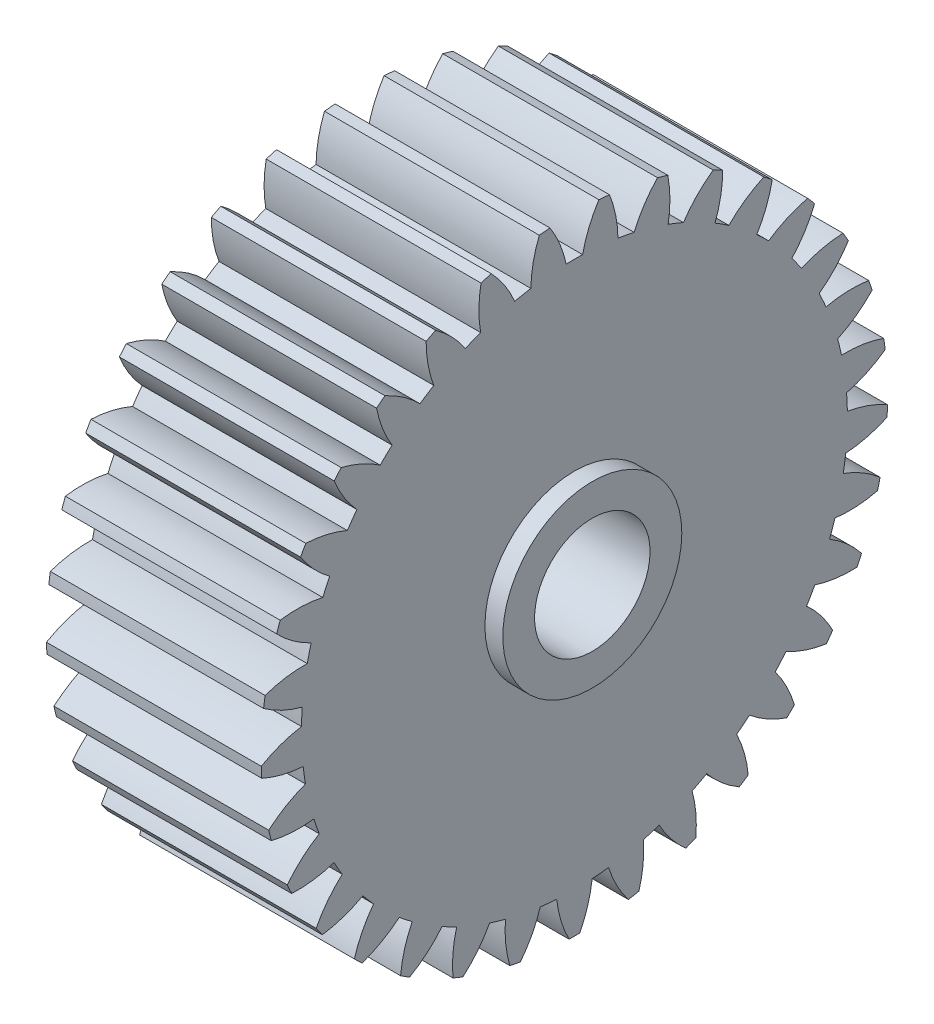
SolidWorks part; units mm, degrees
ref_plane "Plane1" through (0, 0, 0) normal (0, 0, 1) x (1, 0, 0)
ref_plane "Plane2" through (0, 0, 0) normal (0, 1, 0) x (1, 0, 0)
ref_plane "Plane3" through (0, 0, 0) normal (1, 0, 0) x (0, 0, -1)
sketch "HoldingSke" plane through (0, 0, 0) normal (0, 1, 0) x (1, 0, 0)
  line L0 (0, 0) -> (0.8387, -0.5446)
  line L1 (-15, 0) -> (100, 0) construction
  line L2 (0, 0) -> (-2.1039, 2.3779)
  line L3 (0, 0) -> (-11.863, 4.5341)
  line L4 (0, 0) -> (7.2428, 4.7035)
  line L5 (0, 0) -> (-46.8476, -17.4728)
  line L6 (0, 0) -> (-6.6317, -4.4744)
  line L7 (-2.1039, 2.3779) -> (8.6586, 51.2059)
  line L8 (-76.2, 54.61) -> (-74.4, 54.61)
  line L9 (-71.009, 38.7566) -> (-53.1078, 45.2721)
  line L10 (-76.2, 71.12) -> (104.1128, 71.12)
  line L11 (0, 0) -> (-8, 0)
  line L12 (-76.2, 101.6) -> (-76.162, 101.6)
  line L13 (24.9733, 27.94) -> (52.9518, 28.4284)
  line L14 (24.9733, 27.94) -> (24.9743, 27.94)
  line L15 (24.9733, 27.94) -> (100.4006, 29.5858)
  line L16 (-63.627, -1) -> (-12.827, -1)
  circle A0 centre (0, 0) radius 5
  circle A1 centre (0, 0) radius 15.249
  circle A2 centre (0, 0) radius 37.5
  circle A3 centre (0, 0) radius 5
  dimension "MHD" = 30.498
  dimension "Hub_dia" = 75
  dimension "Bore" = 10
  dimension "MBD" = 10
  dimension "Num_teeth" = 33
  dimension "Pitch" = 1
  dimension "Overall_len" = 50
  dimension "Show_teeth" = 33
  dimension "Thickness" = 8
  dimension "OAL" = 50.0001
  dimension "T_dim" = 1.8
  dimension "Ap" = 20
  dimension "H" = 19.05
  dimension "Pitch_radius" = 180.3128
  dimension "Width" = 8
  dimension "Backlash" = 0.038
  dimension "Addendum_fac" = 1
  dimension "Dedendum_fac" = 1.25
  dimension "Clearance_fac" = 0.25
  dimension "Dedendum_add" = 0.001
  dimension "Module" = 1
sketch "BasProSke" plane through (0, 0, 0) normal (0, 1, 0) x (1, 0, 0)
  line L0 (-10, 0) -> (60, 0) construction
  line L1 (0, 0) -> (0, 17.5)
  line L2 (0, 0) -> (6, 0)
  line L3 (6, 0) -> (6, 17.5)
  line L4 (6, 17.5) -> (0, 17.5)
  dimension "Thickness" = 6
  dimension "Diameter" = 35
revolve "Base-Revolve" add sketch "BasProSke" angle 360 about L0
sketch "TooCutSke" plane through (0, 0, 0) normal (1, 0, 0) x (0, 0, -1)
  line L1 (0, 0) -> (0, 107) construction
  line L2 (0, 0) -> (-0.8516, 16.478) construction
  line L3 (0, 0) -> (-3.1339, 32.8194) construction
  line L4 (-0.8516, 16.478) -> (-1.5669, 16.4097) construction
  arc A0 (0.46, 15.2421) -> (-0.46, 15.2421) centre (0, 0) ccw
  arc A1 (1.3819, 17.4708) -> (-1.3819, 17.4708) centre (0, 0) ccw
  circle A2 centre (0, 0) radius 16.5 construction
  circle A3 centre (0, 0) radius 15.5049 construction
  arc A4 (-0.46, 15.2421) -> (-1.3819, 17.4708) centre (-6.9172, 13.8764) ccw
  arc A5 (1.3819, 17.4708) -> (0.46, 15.2421) centre (6.9172, 13.8764) ccw
  dimension "Root_dia" = 30.498
  dimension "Overcut_dia" = 35.0508
  dimension "Pitch_dia" = 33
  dimension "Base_dia" = 31.0099
  dimension "Flank_rad" = 6.6
  dimension "Half_ang" = 5.455
  dimension "Half_CT" = 0.7186
extrude "ToothCut" cut sketch "TooCutSke" along normal through all
fillet "Breaks" [suppressed] radius 0.02 tangent propagation no
fillet "RootFillets" [suppressed] radius 0.251
pattern_circular "TeethCuts" count 33 every 10.909 about axis through (-10, 0, 0) along (1, 0, 0) of "ToothCut", "RootFillets", "Breaks"
sketch "HubNeaOneSke" plane through (0, 0, 0) normal (-1, 0, 0) x (0, 0, 1)
  circle A0 centre (0, 0) radius 15.249
  dimension "Diameter" = 30.498
extrude "HubNearOne" [suppressed] add sketch "HubNeaOneSke" along normal blind 44.0001
sketch "HubNeaBotSke" plane through (0, 0, 0) normal (-1, 0, 0) x (0, 0, 1)
  circle A0 centre (0, 0) radius 15.249
  dimension "Diameter" = 30.498
extrude "HubNearBoth" [suppressed] add sketch "HubNeaBotSke" along normal blind 22
ref_plane "FarPln" through (6, 0, 0) normal (1, 0, 0) x (0, 0, -1)
sketch "HubFarSke" plane through (6, 0, 0) normal (1, 0, 0) x (0, 0, -1)
  circle A0 centre (0, 0) radius 15.249
  dimension "Diameter" = 30.498
extrude "HubFar" [suppressed] add sketch "HubFarSke" along normal blind 22
sketch "BorSke" plane through (0, 0, 0) normal (1, 0, 0) x (0, 0, -1)
  circle A0 centre (0, 0) radius 5
  dimension "Diameter" = 10
extrude "Bore" cut sketch "BorSke" along normal mid plane 100.0001
sketch "KeySke" plane through (0, 0, 0) normal (1, 0, 0) x (0, 0, -1)
  line L0 (-2, 0) -> (-2, 6.8)
  line L1 (-2, 6.8) -> (2, 6.8)
  line L2 (2, 6.8) -> (2, 0)
  line L3 (0, 0) -> (0, 34) construction
  line L4 (-2, 0) -> (2, 0)
  dimension "Offset" = 6.8
  dimension "Width" = 4
extrude "Keyway" [suppressed] cut sketch "KeySke" along normal mid plane 100.0001
pattern_circular "Keyway2" [suppressed] count 2 every 90 about axis through (-10, 0, 0) along (1, 0, 0) reverse direction yes
sketch "Croquis1" plane through (6, 0, 0) normal (1, 0, 0) x (0, 0, -1)
  circle A0 centre (0, 0) radius 5 construction
  circle A1 centre (0, 0) radius 5
  circle A2 centre (0, 0) radius 3.225
  dimension "D1" = 6.45
extrude "Saliente-Extruir2" add sketch "Croquis1" along normal blind 1 and the other way through all
sketch "Croquis2" plane through (0, 0, 0) normal (-1, 0, 0) x (0, 0, 1)
  circle A0 centre (0, 0) radius 3.225 construction
  circle A1 centre (0, 0) radius 3.225
  arc A132 (15.2029, 1.1848) -> (17.3618, 2.1948) centre (13.5316, 7.5696) ccw
  arc A133 (17.3618, 2.1948) -> (17.2769, 2.7855) centre (0, 0) ccw
  arc A134 (17.2769, 2.7855) -> (14.9209, 3.1464) centre (15.1161, -3.4507) ccw
  arc A135 (14.9209, 3.1464) -> (14.704, 4.0405) centre (0, 0) ccw
  arc A136 (14.704, 4.0405) -> (16.6327, 5.4409) centre (11.8545, 9.9937) ccw
  arc A137 (16.6327, 5.4409) -> (16.4375, 6.0049) centre (0, 0) ccw
  arc A138 (16.4375, 6.0049) -> (14.0558, 5.9133) centre (15.4959, -0.5276) ccw
  arc A139 (14.0558, 5.9133) -> (13.6736, 6.7502) centre (0, 0) ccw
  arc A140 (13.6736, 6.7502) -> (15.3024, 8.4903) centre (9.7489, 12.0566) ccw
  arc A141 (15.3024, 8.4903) -> (15.004, 9.0072) centre (0, 0) ccw
  arc A142 (15.004, 9.0072) -> (12.6827, 8.4665) centre (15.3158, 2.4145) ccw
  arc A143 (12.6827, 8.4665) -> (12.149, 9.216) centre (0, 0) ccw
  arc A144 (12.149, 9.216) -> (13.4191, 11.2329) centre (7.291, 13.6837) ccw
  arc A145 (13.4191, 11.2329) -> (13.0283, 11.6839) centre (0, 0) ccw
  arc A146 (13.0283, 11.6839) -> (10.8512, 10.7137) centre (14.582, 5.2694) ccw
  arc A147 (10.8512, 10.7137) -> (10.1853, 11.3487) centre (0, 0) ccw
  arc A148 (10.1853, 11.3487) -> (11.0508, 13.5695) centre (4.5696, 14.8163) ccw
  arc A149 (11.0508, 13.5695) -> (10.5816, 13.9384) centre (0, 0) ccw
  arc A150 (10.5816, 13.9384) -> (8.6275, 12.5737) centre (13.3213, 7.9339) ccw
  arc A151 (8.6275, 12.5737) -> (7.8535, 13.0712) centre (0, 0) ccw
  arc A152 (7.8535, 13.0712) -> (8.283, 15.4156) centre (1.683, 15.4133) ccw
  arc A153 (8.283, 15.4156) -> (7.7526, 15.6891) centre (0, 0) ccw
  arc A154 (7.7526, 15.6891) -> (6.092, 13.9793) centre (11.5791, 10.3116) ccw
  arc A155 (6.092, 13.9793) -> (5.2378, 14.3212) centre (0, 0) ccw
  arc A156 (5.2378, 14.3212) -> (5.2159, 16.7046) centre (-1.2644, 15.4533) ccw
  arc A157 (5.2159, 16.7046) -> (4.6433, 16.8728) centre (0, 0) ccw
  arc A158 (4.6433, 16.8728) -> (3.3363, 14.8796) centre (9.4183, 12.3166) ccw
  arc A159 (3.3363, 14.8796) -> (2.4329, 15.0537) centre (0, 0) ccw
  arc A160 (2.4329, 15.0537) -> (1.9603, 17.3899) centre (-4.1661, 14.9347) ccw
  arc A161 (1.9603, 17.3899) -> (1.3662, 17.4466) centre (0, 0) ccw
  arc A162 (1.3662, 17.4466) -> (0.46, 15.2421) centre (6.9172, 13.8764) ccw
  arc A163 (0.46, 15.2421) -> (-0.46, 15.2421) centre (0, 0) ccw
  arc A164 (-0.46, 15.2421) -> (-1.3662, 17.4466) centre (-6.9172, 13.8764) ccw
  arc A165 (-1.3662, 17.4466) -> (-1.9603, 17.3899) centre (0, 0) ccw
  arc A166 (-1.9603, 17.3899) -> (-2.4329, 15.0537) centre (4.1661, 14.9347) ccw
  arc A167 (-2.4329, 15.0537) -> (-3.3363, 14.8796) centre (0, 0) ccw
  arc A168 (-3.3363, 14.8796) -> (-4.6433, 16.8728) centre (-9.4183, 12.3166) ccw
  arc A169 (-4.6433, 16.8728) -> (-5.2159, 16.7046) centre (0, 0) ccw
  arc A170 (-5.2159, 16.7046) -> (-5.2378, 14.3212) centre (1.2644, 15.4533) ccw
  arc A171 (-5.2378, 14.3212) -> (-6.092, 13.9793) centre (0, 0) ccw
  arc A172 (-6.092, 13.9793) -> (-7.7526, 15.6891) centre (-11.5791, 10.3116) ccw
  arc A173 (-7.7526, 15.6891) -> (-8.283, 15.4156) centre (0, 0) ccw
  arc A174 (-8.283, 15.4156) -> (-7.8535, 13.0712) centre (-1.683, 15.4133) ccw
  arc A175 (-7.8535, 13.0712) -> (-8.6275, 12.5737) centre (0, 0) ccw
  arc A176 (-8.6275, 12.5737) -> (-10.5816, 13.9384) centre (-13.3213, 7.9339) ccw
  arc A177 (-10.5816, 13.9384) -> (-11.0508, 13.5695) centre (0, 0) ccw
  arc A178 (-11.0508, 13.5695) -> (-10.1853, 11.3487) centre (-4.5696, 14.8163) ccw
  arc A179 (-10.1853, 11.3487) -> (-10.8512, 10.7137) centre (0, 0) ccw
  arc A180 (-10.8512, 10.7137) -> (-13.0283, 11.6839) centre (-14.582, 5.2694) ccw
  arc A181 (-13.0283, 11.6839) -> (-13.4191, 11.2329) centre (0, 0) ccw
  arc A182 (-13.4191, 11.2329) -> (-12.149, 9.216) centre (-7.291, 13.6837) ccw
  arc A183 (-12.149, 9.216) -> (-12.6827, 8.4665) centre (0, 0) ccw
  arc A184 (-12.6827, 8.4665) -> (-15.004, 9.0072) centre (-15.3158, 2.4145) ccw
  arc A185 (-15.004, 9.0072) -> (-15.3024, 8.4903) centre (0, 0) ccw
  arc A186 (-15.3024, 8.4903) -> (-13.6736, 6.7502) centre (-9.7489, 12.0566) ccw
  arc A187 (-13.6736, 6.7502) -> (-14.0558, 5.9133) centre (0, 0) ccw
  arc A188 (-14.0558, 5.9133) -> (-16.4375, 6.0049) centre (-15.4959, -0.5276) ccw
  arc A189 (-16.4375, 6.0049) -> (-16.6327, 5.4409) centre (0, 0) ccw
  arc A190 (-16.6327, 5.4409) -> (-14.704, 4.0405) centre (-11.8545, 9.9937) ccw
  arc A191 (-14.704, 4.0405) -> (-14.9209, 3.1464) centre (0, 0) ccw
  arc A192 (-14.9209, 3.1464) -> (-17.2769, 2.7855) centre (-15.1161, -3.4507) ccw
  arc A193 (-17.2769, 2.7855) -> (-17.3618, 2.1948) centre (0, 0) ccw
  arc A194 (-17.3618, 2.1948) -> (-15.2029, 1.1848) centre (-13.5316, 7.5696) ccw
  arc A195 (-15.2029, 1.1848) -> (-15.2467, 0.2657) centre (0, 0) ccw
  arc A196 (-15.2467, 0.2657) -> (-17.4918, -0.5345) centre (-14.1898, -6.2491) ccw
  arc A197 (-17.4918, -0.5345) -> (-17.4634, -1.1306) centre (0, 0) ccw
  arc A198 (-17.4634, -1.1306) -> (-15.1524, -1.7138) centre (-14.7196, 4.872) ccw
  arc A199 (-15.1524, -1.7138) -> (-15.0214, -2.6245) centre (0, 0) ccw
  arc A200 (-15.0214, -2.6245) -> (-17.0746, -3.8352) centre (-12.7508, -8.8216) ccw
  arc A201 (-17.0746, -3.8352) -> (-16.9339, -4.4152) centre (0, 0) ccw
  arc A202 (-16.9339, -4.4152) -> (-14.5542, -4.5505) centre (-15.3756, 1.9982) ccw
  arc A203 (-14.5542, -4.5505) -> (-14.2533, -5.4199) centre (0, 0) ccw
  arc A204 (-14.2533, -5.4199) -> (-16.0402, -6.9973) centre (-10.8508, -11.0753) ccw
  arc A205 (-16.0402, -6.9973) -> (-15.7923, -7.5401) centre (0, 0) ccw
  arc A206 (-15.7923, -7.5401) -> (-13.43, -7.2226) centre (-15.4759, -0.9477) ccw
  arc A207 (-13.43, -7.2226) -> (-12.97, -8.0194) centre (0, 0) ccw
  arc A208 (-12.97, -8.0194) -> (-14.4261, -9.9064) centre (-8.5587, -12.9287) ccw
  arc A209 (-14.4261, -9.9064) -> (-14.0799, -10.3926) centre (0, 0) ccw
  arc A210 (-14.0799, -10.3926) -> (-11.8204, -9.6338) centre (-15.0169, -3.8594) ccw
  arc A211 (-11.8204, -9.6338) -> (-11.2179, -10.3291) centre (0, 0) ccw
  arc A212 (-11.2179, -10.3291) -> (-12.2906, -12.4576) centre (-5.9573, -14.3148) ccw
  arc A213 (-12.2906, -12.4576) -> (-11.8587, -12.8694) centre (0, 0) ccw
  arc A214 (-11.8587, -12.8694) -> (-9.7836, -11.6967) centre (-14.0151, -6.6317) ccw
  arc A215 (-9.7836, -11.6967) -> (-9.0604, -12.2654) centre (0, 0) ccw
  arc A216 (-9.0604, -12.2654) -> (-9.7109, -14.5585) centre (-3.1405, -15.1835) ccw
  arc A217 (-9.7109, -14.5585) -> (-9.2088, -14.8811) centre (0, 0) ccw
  arc A218 (-9.2088, -14.8811) -> (-7.3932, -13.3369) centre (-12.5068, -9.1642) ccw
  arc A219 (-7.3932, -13.3369) -> (-6.5754, -13.7585) centre (0, 0) ccw
  arc A220 (-6.5754, -13.7585) -> (-6.7802, -16.1332) centre (-0.2103, -15.5035) ccw
  arc A221 (-6.7802, -16.1332) -> (-6.2261, -16.355) centre (0, 0) ccw
  arc A222 (-6.2261, -16.355) -> (-4.7356, -14.495) centre (-10.5465, -11.3655) ccw
  arc A223 (-4.7356, -14.495) -> (-3.8528, -14.7543) centre (0, 0) ccw
  arc A224 (-3.8528, -14.7543) -> (-3.6044, -17.1248) centre (2.7276, -15.2631) ccw
  arc A225 (-3.6044, -17.1248) -> (-3.0184, -17.2377) centre (0, 0) ccw
  arc A226 (-3.0184, -17.2377) -> (-1.9068, -15.1293) centre (-8.2049, -13.1561) ccw
  arc A227 (-1.9068, -15.1293) -> (-0.9909, -15.2168) centre (0, 0) ccw
  arc A228 (-0.9909, -15.2168) -> (-0.2984, -17.4975) centre (5.5668, -14.4711) ccw
  arc A229 (-0.2984, -17.4975) -> (0.2984, -17.4975) centre (0, 0) ccw
  arc A230 (0.2984, -17.4975) -> (0.9909, -15.2168) centre (-5.5668, -14.4711) ccw
  arc A231 (0.9909, -15.2168) -> (1.9068, -15.1293) centre (0, 0) ccw
  arc A232 (1.9068, -15.1293) -> (3.0184, -17.2377) centre (8.2049, -13.1561) ccw
  arc A233 (3.0184, -17.2377) -> (3.6044, -17.1248) centre (0, 0) ccw
  arc A234 (3.6044, -17.1248) -> (3.8528, -14.7543) centre (-2.7276, -15.2631) ccw
  arc A235 (3.8528, -14.7543) -> (4.7356, -14.495) centre (0, 0) ccw
  arc A236 (4.7356, -14.495) -> (6.2261, -16.355) centre (10.5465, -11.3655) ccw
  arc A237 (6.2261, -16.355) -> (6.7802, -16.1332) centre (0, 0) ccw
  arc A238 (6.7802, -16.1332) -> (6.5754, -13.7585) centre (0.2103, -15.5035) ccw
  arc A239 (6.5754, -13.7585) -> (7.3932, -13.3369) centre (0, 0) ccw
  arc A240 (7.3932, -13.3369) -> (9.2088, -14.8811) centre (12.5068, -9.1642) ccw
  arc A241 (9.2088, -14.8811) -> (9.7109, -14.5585) centre (0, 0) ccw
  arc A242 (9.7109, -14.5585) -> (9.0604, -12.2654) centre (3.1405, -15.1835) ccw
  arc A243 (9.0604, -12.2654) -> (9.7836, -11.6967) centre (0, 0) ccw
  arc A244 (9.7836, -11.6967) -> (11.8587, -12.8694) centre (14.0151, -6.6317) ccw
  arc A245 (11.8587, -12.8694) -> (12.2906, -12.4576) centre (0, 0) ccw
  arc A246 (12.2906, -12.4576) -> (11.2179, -10.3291) centre (5.9573, -14.3148) ccw
  arc A247 (11.2179, -10.3291) -> (11.8204, -9.6338) centre (0, 0) ccw
  arc A248 (11.8204, -9.6338) -> (14.0799, -10.3926) centre (15.0169, -3.8594) ccw
  arc A249 (14.0799, -10.3926) -> (14.4261, -9.9064) centre (0, 0) ccw
  arc A250 (14.4261, -9.9064) -> (12.97, -8.0194) centre (8.5587, -12.9287) ccw
  arc A251 (12.97, -8.0194) -> (13.43, -7.2226) centre (0, 0) ccw
  arc A252 (13.43, -7.2226) -> (15.7923, -7.5401) centre (15.4759, -0.9477) ccw
  arc A253 (15.7923, -7.5401) -> (16.0402, -6.9973) centre (0, 0) ccw
  arc A254 (16.0402, -6.9973) -> (14.2533, -5.4199) centre (10.8508, -11.0753) ccw
  arc A255 (14.2533, -5.4199) -> (14.5542, -4.5505) centre (0, 0) ccw
  arc A256 (14.5542, -4.5505) -> (16.9339, -4.4152) centre (15.3756, 1.9982) ccw
  arc A257 (16.9339, -4.4152) -> (17.0746, -3.8352) centre (0, 0) ccw
  arc A258 (17.0746, -3.8352) -> (15.0214, -2.6245) centre (12.7508, -8.8216) ccw
  arc A259 (15.0214, -2.6245) -> (15.1524, -1.7138) centre (0, 0) ccw
  arc A260 (15.1524, -1.7138) -> (17.4634, -1.1306) centre (14.7196, 4.872) ccw
  arc A261 (17.4634, -1.1306) -> (17.4918, -0.5345) centre (0, 0) ccw
  arc A262 (17.4918, -0.5345) -> (15.2467, 0.2657) centre (14.1898, -6.2491) ccw
  arc A263 (15.2467, 0.2657) -> (15.2029, 1.1848) centre (0, 0) ccw
  arc A264 (15.2029, 1.1848) -> (17.3618, 2.1948) centre (13.5316, 7.5696) ccw
  arc A265 (17.3618, 2.1948) -> (17.2769, 2.7855) centre (0, 0) ccw
  arc A266 (17.2769, 2.7855) -> (14.9209, 3.1464) centre (15.1161, -3.4507) ccw
  arc A267 (14.9209, 3.1464) -> (14.704, 4.0405) centre (0, 0) ccw
  arc A268 (14.704, 4.0405) -> (16.6327, 5.4409) centre (11.8545, 9.9937) ccw
  arc A269 (16.6327, 5.4409) -> (16.4375, 6.0049) centre (0, 0) ccw
  arc A270 (16.4375, 6.0049) -> (14.0558, 5.9133) centre (15.4959, -0.5276) ccw
  arc A271 (14.0558, 5.9133) -> (13.6736, 6.7502) centre (0, 0) ccw
  arc A272 (13.6736, 6.7502) -> (15.3024, 8.4903) centre (9.7489, 12.0566) ccw
  arc A273 (15.3024, 8.4903) -> (15.004, 9.0072) centre (0, 0) ccw
  arc A274 (15.004, 9.0072) -> (12.6827, 8.4665) centre (15.3158, 2.4145) ccw
  arc A275 (12.6827, 8.4665) -> (12.149, 9.216) centre (0, 0) ccw
  arc A276 (12.149, 9.216) -> (13.4191, 11.2329) centre (7.291, 13.6837) ccw
  arc A277 (13.4191, 11.2329) -> (13.0283, 11.6839) centre (0, 0) ccw
  arc A278 (13.0283, 11.6839) -> (10.8512, 10.7137) centre (14.582, 5.2694) ccw
  arc A279 (10.8512, 10.7137) -> (10.1853, 11.3487) centre (0, 0) ccw
  arc A280 (10.1853, 11.3487) -> (11.0508, 13.5695) centre (4.5696, 14.8163) ccw
  arc A281 (11.0508, 13.5695) -> (10.5816, 13.9384) centre (0, 0) ccw
  arc A282 (10.5816, 13.9384) -> (8.6275, 12.5737) centre (13.3213, 7.9339) ccw
  arc A283 (8.6275, 12.5737) -> (7.8535, 13.0712) centre (0, 0) ccw
  arc A284 (7.8535, 13.0712) -> (8.283, 15.4156) centre (1.683, 15.4133) ccw
  arc A285 (8.283, 15.4156) -> (7.7526, 15.6891) centre (0, 0) ccw
  arc A286 (7.7526, 15.6891) -> (6.092, 13.9793) centre (11.5791, 10.3116) ccw
  arc A287 (6.092, 13.9793) -> (5.2378, 14.3212) centre (0, 0) ccw
  arc A288 (5.2378, 14.3212) -> (5.2159, 16.7046) centre (-1.2644, 15.4533) ccw
  arc A289 (5.2159, 16.7046) -> (4.6433, 16.8728) centre (0, 0) ccw
  arc A290 (4.6433, 16.8728) -> (3.3363, 14.8796) centre (9.4183, 12.3166) ccw
  arc A291 (3.3363, 14.8796) -> (2.4329, 15.0537) centre (0, 0) ccw
  arc A292 (2.4329, 15.0537) -> (1.9603, 17.3899) centre (-4.1661, 14.9347) ccw
  arc A293 (1.9603, 17.3899) -> (1.3662, 17.4466) centre (0, 0) ccw
  arc A294 (1.3662, 17.4466) -> (0.46, 15.2421) centre (6.9172, 13.8764) ccw
  arc A295 (0.46, 15.2421) -> (-0.46, 15.2421) centre (0, 0) ccw
  arc A296 (-0.46, 15.2421) -> (-1.3662, 17.4466) centre (-6.9172, 13.8764) ccw
  arc A297 (-1.3662, 17.4466) -> (-1.9603, 17.3899) centre (0, 0) ccw
  arc A298 (-1.9603, 17.3899) -> (-2.4329, 15.0537) centre (4.1661, 14.9347) ccw
  arc A299 (-2.4329, 15.0537) -> (-3.3363, 14.8796) centre (0, 0) ccw
  arc A300 (-3.3363, 14.8796) -> (-4.6433, 16.8728) centre (-9.4183, 12.3166) ccw
  arc A301 (-4.6433, 16.8728) -> (-5.2159, 16.7046) centre (0, 0) ccw
  arc A302 (-5.2159, 16.7046) -> (-5.2378, 14.3212) centre (1.2644, 15.4533) ccw
  arc A303 (-5.2378, 14.3212) -> (-6.092, 13.9793) centre (0, 0) ccw
  arc A304 (-6.092, 13.9793) -> (-7.7526, 15.6891) centre (-11.5791, 10.3116) ccw
  arc A305 (-7.7526, 15.6891) -> (-8.283, 15.4156) centre (0, 0) ccw
  arc A306 (-8.283, 15.4156) -> (-7.8535, 13.0712) centre (-1.683, 15.4133) ccw
  arc A307 (-7.8535, 13.0712) -> (-8.6275, 12.5737) centre (0, 0) ccw
  arc A308 (-8.6275, 12.5737) -> (-10.5816, 13.9384) centre (-13.3213, 7.9339) ccw
  arc A309 (-10.5816, 13.9384) -> (-11.0508, 13.5695) centre (0, 0) ccw
  arc A310 (-11.0508, 13.5695) -> (-10.1853, 11.3487) centre (-4.5696, 14.8163) ccw
  arc A311 (-10.1853, 11.3487) -> (-10.8512, 10.7137) centre (0, 0) ccw
  arc A312 (-10.8512, 10.7137) -> (-13.0283, 11.6839) centre (-14.582, 5.2694) ccw
  arc A313 (-13.0283, 11.6839) -> (-13.4191, 11.2329) centre (0, 0) ccw
  arc A314 (-13.4191, 11.2329) -> (-12.149, 9.216) centre (-7.291, 13.6837) ccw
  arc A315 (-12.149, 9.216) -> (-12.6827, 8.4665) centre (0, 0) ccw
  arc A316 (-12.6827, 8.4665) -> (-15.004, 9.0072) centre (-15.3158, 2.4145) ccw
  arc A317 (-15.004, 9.0072) -> (-15.3024, 8.4903) centre (0, 0) ccw
  arc A318 (-15.3024, 8.4903) -> (-13.6736, 6.7502) centre (-9.7489, 12.0566) ccw
  arc A319 (-13.6736, 6.7502) -> (-14.0558, 5.9133) centre (0, 0) ccw
  arc A320 (-14.0558, 5.9133) -> (-16.4375, 6.0049) centre (-15.4959, -0.5276) ccw
  arc A321 (-16.4375, 6.0049) -> (-16.6327, 5.4409) centre (0, 0) ccw
  arc A322 (-16.6327, 5.4409) -> (-14.704, 4.0405) centre (-11.8545, 9.9937) ccw
  arc A323 (-14.704, 4.0405) -> (-14.9209, 3.1464) centre (0, 0) ccw
  arc A324 (-14.9209, 3.1464) -> (-17.2769, 2.7855) centre (-15.1161, -3.4507) ccw
  arc A325 (-17.2769, 2.7855) -> (-17.3618, 2.1948) centre (0, 0) ccw
  arc A326 (-17.3618, 2.1948) -> (-15.2029, 1.1848) centre (-13.5316, 7.5696) ccw
  arc A327 (-15.2029, 1.1848) -> (-15.2467, 0.2657) centre (0, 0) ccw
  arc A328 (-15.2467, 0.2657) -> (-17.4918, -0.5345) centre (-14.1898, -6.2491) ccw
  arc A329 (-17.4918, -0.5345) -> (-17.4634, -1.1306) centre (0, 0) ccw
  arc A330 (-17.4634, -1.1306) -> (-15.1524, -1.7138) centre (-14.7196, 4.872) ccw
  arc A331 (-15.1524, -1.7138) -> (-15.0214, -2.6245) centre (0, 0) ccw
  arc A332 (-15.0214, -2.6245) -> (-17.0746, -3.8352) centre (-12.7508, -8.8216) ccw
  arc A333 (-17.0746, -3.8352) -> (-16.9339, -4.4152) centre (0, 0) ccw
  arc A334 (-16.9339, -4.4152) -> (-14.5542, -4.5505) centre (-15.3756, 1.9982) ccw
  arc A335 (-14.5542, -4.5505) -> (-14.2533, -5.4199) centre (0, 0) ccw
  arc A336 (-14.2533, -5.4199) -> (-16.0402, -6.9973) centre (-10.8508, -11.0753) ccw
  arc A337 (-16.0402, -6.9973) -> (-15.7923, -7.5401) centre (0, 0) ccw
  arc A338 (-15.7923, -7.5401) -> (-13.43, -7.2226) centre (-15.4759, -0.9477) ccw
  arc A339 (-13.43, -7.2226) -> (-12.97, -8.0194) centre (0, 0) ccw
  arc A340 (-12.97, -8.0194) -> (-14.4261, -9.9064) centre (-8.5587, -12.9287) ccw
  arc A341 (-14.4261, -9.9064) -> (-14.0799, -10.3926) centre (0, 0) ccw
  arc A342 (-14.0799, -10.3926) -> (-11.8204, -9.6338) centre (-15.0169, -3.8594) ccw
  arc A343 (-11.8204, -9.6338) -> (-11.2179, -10.3291) centre (0, 0) ccw
  arc A344 (-11.2179, -10.3291) -> (-12.2906, -12.4576) centre (-5.9573, -14.3148) ccw
  arc A345 (-12.2906, -12.4576) -> (-11.8587, -12.8694) centre (0, 0) ccw
  arc A346 (-11.8587, -12.8694) -> (-9.7836, -11.6967) centre (-14.0151, -6.6317) ccw
  arc A347 (-9.7836, -11.6967) -> (-9.0604, -12.2654) centre (0, 0) ccw
  arc A348 (-9.0604, -12.2654) -> (-9.7109, -14.5585) centre (-3.1405, -15.1835) ccw
  arc A349 (-9.7109, -14.5585) -> (-9.2088, -14.8811) centre (0, 0) ccw
  arc A350 (-9.2088, -14.8811) -> (-7.3932, -13.3369) centre (-12.5068, -9.1642) ccw
  arc A351 (-7.3932, -13.3369) -> (-6.5754, -13.7585) centre (0, 0) ccw
  arc A352 (-6.5754, -13.7585) -> (-6.7802, -16.1332) centre (-0.2103, -15.5035) ccw
  arc A353 (-6.7802, -16.1332) -> (-6.2261, -16.355) centre (0, 0) ccw
  arc A354 (-6.2261, -16.355) -> (-4.7356, -14.495) centre (-10.5465, -11.3655) ccw
  arc A355 (-4.7356, -14.495) -> (-3.8528, -14.7543) centre (0, 0) ccw
  arc A356 (-3.8528, -14.7543) -> (-3.6044, -17.1248) centre (2.7276, -15.2631) ccw
  arc A357 (-3.6044, -17.1248) -> (-3.0184, -17.2377) centre (0, 0) ccw
  arc A358 (-3.0184, -17.2377) -> (-1.9068, -15.1293) centre (-8.2049, -13.1561) ccw
  arc A359 (-1.9068, -15.1293) -> (-0.9909, -15.2168) centre (0, 0) ccw
  arc A360 (-0.9909, -15.2168) -> (-0.2984, -17.4975) centre (5.5668, -14.4711) ccw
  arc A361 (-0.2984, -17.4975) -> (0.2984, -17.4975) centre (0, 0) ccw
  arc A362 (0.2984, -17.4975) -> (0.9909, -15.2168) centre (-5.5668, -14.4711) ccw
  arc A363 (0.9909, -15.2168) -> (1.9068, -15.1293) centre (0, 0) ccw
  arc A364 (1.9068, -15.1293) -> (3.0184, -17.2377) centre (8.2049, -13.1561) ccw
  arc A365 (3.0184, -17.2377) -> (3.6044, -17.1248) centre (0, 0) ccw
  arc A366 (3.6044, -17.1248) -> (3.8528, -14.7543) centre (-2.7276, -15.2631) ccw
  arc A367 (3.8528, -14.7543) -> (4.7356, -14.495) centre (0, 0) ccw
  arc A368 (4.7356, -14.495) -> (6.2261, -16.355) centre (10.5465, -11.3655) ccw
  arc A369 (6.2261, -16.355) -> (6.7802, -16.1332) centre (0, 0) ccw
  arc A370 (6.7802, -16.1332) -> (6.5754, -13.7585) centre (0.2103, -15.5035) ccw
  arc A371 (6.5754, -13.7585) -> (7.3932, -13.3369) centre (0, 0) ccw
  arc A372 (7.3932, -13.3369) -> (9.2088, -14.8811) centre (12.5068, -9.1642) ccw
  arc A373 (9.2088, -14.8811) -> (9.7109, -14.5585) centre (0, 0) ccw
  arc A374 (9.7109, -14.5585) -> (9.0604, -12.2654) centre (3.1405, -15.1835) ccw
  arc A375 (9.0604, -12.2654) -> (9.7836, -11.6967) centre (0, 0) ccw
  arc A376 (9.7836, -11.6967) -> (11.8587, -12.8694) centre (14.0151, -6.6317) ccw
  arc A377 (11.8587, -12.8694) -> (12.2906, -12.4576) centre (0, 0) ccw
  arc A378 (12.2906, -12.4576) -> (11.2179, -10.3291) centre (5.9573, -14.3148) ccw
  arc A379 (11.2179, -10.3291) -> (11.8204, -9.6338) centre (0, 0) ccw
  arc A380 (11.8204, -9.6338) -> (14.0799, -10.3926) centre (15.0169, -3.8594) ccw
  arc A381 (14.0799, -10.3926) -> (14.4261, -9.9064) centre (0, 0) ccw
  arc A382 (14.4261, -9.9064) -> (12.97, -8.0194) centre (8.5587, -12.9287) ccw
  arc A383 (12.97, -8.0194) -> (13.43, -7.2226) centre (0, 0) ccw
  arc A384 (13.43, -7.2226) -> (15.7923, -7.5401) centre (15.4759, -0.9477) ccw
  arc A385 (15.7923, -7.5401) -> (16.0402, -6.9973) centre (0, 0) ccw
  arc A386 (16.0402, -6.9973) -> (14.2533, -5.4199) centre (10.8508, -11.0753) ccw
  arc A387 (14.2533, -5.4199) -> (14.5542, -4.5505) centre (0, 0) ccw
  arc A388 (14.5542, -4.5505) -> (16.9339, -4.4152) centre (15.3756, 1.9982) ccw
  arc A389 (16.9339, -4.4152) -> (17.0746, -3.8352) centre (0, 0) ccw
  arc A390 (17.0746, -3.8352) -> (15.0214, -2.6245) centre (12.7508, -8.8216) ccw
  arc A391 (15.0214, -2.6245) -> (15.1524, -1.7138) centre (0, 0) ccw
  arc A392 (15.1524, -1.7138) -> (17.4634, -1.1306) centre (14.7196, 4.872) ccw
  arc A393 (17.4634, -1.1306) -> (17.4918, -0.5345) centre (0, 0) ccw
  arc A394 (17.4918, -0.5345) -> (15.2467, 0.2657) centre (14.1898, -6.2491) ccw
  arc A395 (15.2467, 0.2657) -> (15.2029, 1.1848) centre (0, 0) ccw
  dimension "D1" = 0
extrude "Saliente-Extruir3" add sketch "Croquis2" along normal blind 6
equation "' \"Module@HoldingSke\" = 6.35"
equation "' \"Num_teeth@HoldingSke\" = 12"
equation "' \"Ap@HoldingSke\" =  20"
equation "' \"Ap@HoldingSke\" = 20"
equation "' \"Width@HoldingSke\" = 0.5 * 25.4"
equation "' \"Hub_dia@HoldingSke\"= 1 * 25.4"
equation "' \"Hub_dia@HoldingSke\" = 1 * 25.4"
equation "' \"Overall_len@HoldingSke\" = 1.0 * 25.4"
equation "' \"Bore@HoldingSke\" = 0.75 * 25.4"
equation "' \"T_dim@HoldingSke\" = 0.1 * 25.4"
equation "' \"Width@KeySke\" = 0.25 * 25.4"
equation "' \"Show_teeth@HoldingSke\" = 13"
equation "' \"Backlash@HoldingSke\" = 0.009 * 25.4"
equation "' \"Addendum_fac@HoldingSke\" = 1.0"
equation "' \"Dedendum_fac@HoldingSke\" = 1.25"
equation "' \"Dedendum_add@HoldingSke\" = 0.00005 * 25.4"
equation "' \"Clearance_fac@HoldingSke\" = 0.25"
equation "\"Pitch@HoldingSke\" = 1 / \"Module@HoldingSke\""
equation "\"Overcut_dia@TooCutSke\" = (\"Num_teeth@HoldingSke\" + 2 * \"Addendum_fac@HoldingSke\") / \"Pitch@HoldingSke\" + 0.002 * 25.4"
equation "\"Pitch_dia@TooCutSke\" = \"Num_teeth@HoldingSke\" / \"Pitch@HoldingSke\""
equation "\"Base_dia@TooCutSke\" = \"Num_teeth@HoldingSke\" / \"Pitch@HoldingSke\" * cos((\"Ap@HoldingSke\"  * 3.14159265 / 180))"
equation "\"Root_dia@TooCutSke\" = (\"Num_teeth@HoldingSke\" + 2) / \"Pitch@HoldingSke\" - 2 * (\"Addendum_fac@HoldingSke\" + \"Dedendum_fac@HoldingSke\") / \"Pitch@HoldingSke\" - \"Dedendum_add@HoldingSke\" * 2"
equation "\"Half_ang@TooCutSke\" = 180 / \"Num_teeth@HoldingSke\""
equation "\"Half_CT@TooCutSke\" = \"Num_teeth@HoldingSke\" / \"Pitch@HoldingSke\" * sin((3.14159265 / 2 / \"Num_teeth@HoldingSke\")) / 2 - 7 * \"Backlash@HoldingSke\" / 4"
equation "\"Flank_rad@TooCutSke\" = \"Num_teeth@HoldingSke\" / \"Pitch@HoldingSke\" / 5"
equation "\"Radius@RootFillets\" = \"Clearance_fac@HoldingSke\" / \"Pitch@HoldingSke\" + \"Dedendum_add@HoldingSke\""
equation "\"Break_rad@Breaks\" = 0.02 / \"Pitch@HoldingSke\""
equation "\"Thickness@HoldingSke\" = \"Width@HoldingSke\""
equation "\"OAL@HoldingSke\" = \"Thickness@HoldingSke\""
equation "\"MHD@HoldingSke\" = (\"Num_teeth@HoldingSke\" + 2) / \"Pitch@HoldingSke\" - 2 * (\"Addendum_fac@HoldingSke\" + \"Dedendum_fac@HoldingSke\")  / \"Pitch@HoldingSke\" - \"Dedendum_add@HoldingSke\" * 2"
equation "\"MBD@HoldingSke\" = (\"Num_teeth@HoldingSke\" + 2) / \"Pitch@HoldingSke\" - 2 * (\"Addendum_fac@HoldingSke\" + \"Dedendum_fac@HoldingSke\")  / \"Pitch@HoldingSke\" - \"Dedendum_add@HoldingSke\" * 2 - 0.002 * 25.4"
equation "\"MHD@HoldingSke\" = ((sgn( \"MHD@HoldingSke\" - \"Hub_dia@HoldingSke\" )-1)*( \"MHD@HoldingSke\" - \"Hub_dia@HoldingSke\" ))/-2+ \"Hub_dia@HoldingSke\""
equation "\"MBD@HoldingSke\" = ((sgn( \"MBD@HoldingSke\" - \"Bore@HoldingSke\" )-1)*( \"MBD@HoldingSke\" - \"Bore@HoldingSke\" ))/-2+ \"Bore@HoldingSke\""
equation "\"OAL@HoldingSke\" = ((sgn( \"OAL@HoldingSke\" - \"Overall_len@HoldingSke\" )+1)*( \"OAL@HoldingSke\" - \"Overall_len@HoldingSke\" ))/2 + \"Overall_len@HoldingSke\" + 0.000002 * 25.4"
equation "\"Num_teeth@TeethCuts\" = int( \"Show_teeth@HoldingSke\" ) + 1"
equation "\"Num_teeth@TeethCuts\" = ((sgn( \"Num_teeth@TeethCuts\" - \"Num_teeth@HoldingSke\" )-1)*( \"Num_teeth@TeethCuts\" - \"Num_teeth@HoldingSke\" ))/-2+ \"Num_teeth@HoldingSke\""
equation "\"Num_teeth@TeethCuts\" = ((sgn( \"Num_teeth@TeethCuts\" - 2.0)+1)*( \"Num_teeth@TeethCuts\" - 2.0))/2 +2.0"
equation "\"Angle@TeethCuts\" = 360.0 / \"Num_teeth@HoldingSke\""
equation "\"Diameter@BasProSke\" = (\"Num_teeth@HoldingSke\" + 2 * \"Addendum_fac@HoldingSke\") / \"Pitch@HoldingSke\""
equation "' \"Fillet_rad@BasProSke\" =  \"Thickness@HoldingSke\" * 0.05"
equation "' \"Fillet_rad@BasProSke\" = \"Thickness@HoldingSke\" * 0.05"
equation "\"MHD@HoldingSke\" = ((sgn( \"MHD@HoldingSke\" - \"Root_dia@TooCutSke\" )-1)*( \"MHD@HoldingSke\" - \"Root_dia@TooCutSke\" ))/-2+ \"Root_dia@TooCutSke\""
equation "\"Diameter@HubNeaOneSke\" = \"MHD@HoldingSke\""
equation "\"Length@HubNearOne\" = \"OAL@HoldingSke\" - \"Thickness@BasProSke\""
equation "\"Diameter@HubNeaBotSke\" = \"MHD@HoldingSke\""
equation "\"Length@HubNearBoth\" = ( \"OAL@HoldingSke\" - \"Thickness@BasProSke\" ) / 2.0"
equation "\"Thickness@FarPln\" = \"Thickness@BasProSke\""
equation "\"Diameter@HubFarSke\" = \"MHD@HoldingSke\""
equation "\"Length@HubFar\" = ( \"OAL@HoldingSke\" - \"Thickness@BasProSke\" ) / 2.0"
equation "\"Diameter@BorSke\" = \"MBD@HoldingSke\""
equation "\"D1@Bore\" = \"OAL@HoldingSke\" * 2.0"
equation "\"D1@Keyway\" = \"OAL@HoldingSke\" * 2.0"
equation "\"Offset@KeySke\" = \"T_dim@HoldingSke\" + \"MBD@HoldingSke\" / 2.0"
